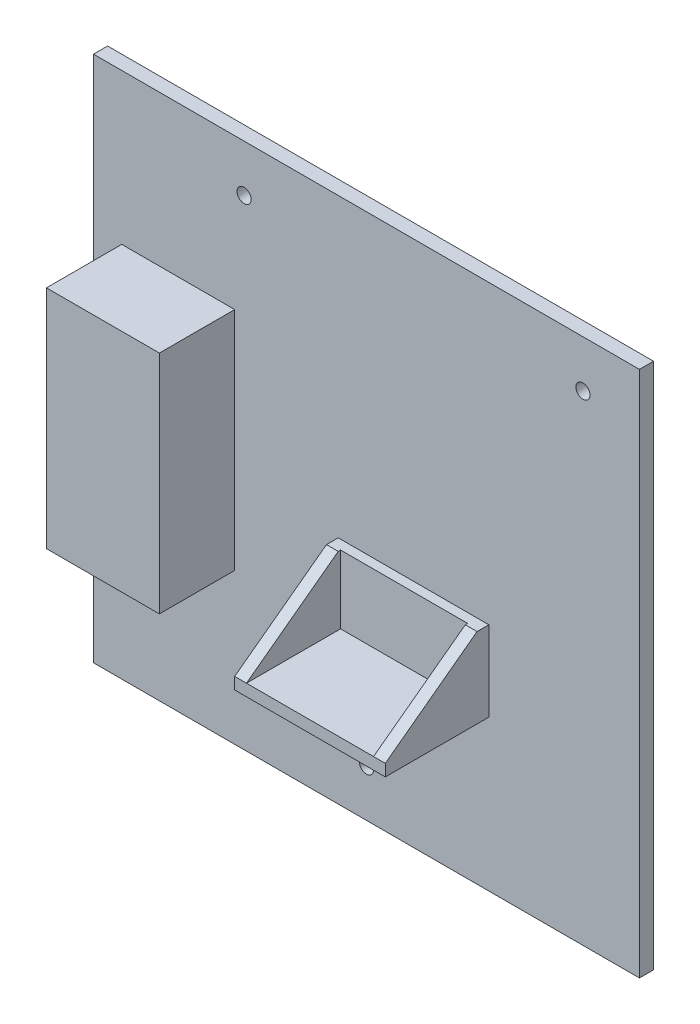
SolidWorks part; units mm, degrees
ref_plane "Alzado" through (0, 0, 0) normal (0, 0, 1) x (1, 0, 0)
ref_plane "Planta" through (0, 0, 0) normal (0, 1, 0) x (1, 0, 0)
ref_plane "Vista lateral" through (0, 0, 0) normal (1, 0, 0) x (0, 0, -1)
sketch "Croquis1" plane through (0, 0, 0) normal (0, 0, 1) x (1, 0, 0)
  line L1 (-58, -56) -> (58, -56)
  line L2 (-58, -56) -> (-58, 56)
  line L3 (-58, 56) -> (58, 56)
  line L4 (58, -56) -> (58, 56)
  line L5 (-58, -56) -> (58, 56) construction
  line L6 (-58, 56) -> (58, -56) construction
  point P0 (0, 0)
  dimension "D1" = 112
  dimension "D2" = 116
extrude "Saliente-Extruir1" add sketch "Croquis1" along normal blind 3
sketch "Croquis2" plane through (0, 0, 3) normal (0, 0, 1) x (1, 0, 0)
  line L0 (-58, 56) -> (-58, -56) construction
  line L1 (-52, -24) -> (-28, -24)
  line L2 (-52, -24) -> (-52, 24)
  line L3 (-52, 24) -> (-28, 24)
  line L4 (-28, -24) -> (-28, 24)
  line L5 (-52, -24) -> (-28, 24) construction
  line L6 (-52, 24) -> (-28, -24) construction
  line L7 (-58, -56) -> (58, -56) construction
  point P0 (-40, 0)
  dimension "D1" = 6
  dimension "D2" = 32
  dimension "D3" = 24
  dimension "D4" = 48
extrude "Saliente-Extruir2" add sketch "Croquis2" along normal blind 16
sketch "Croquis3" plane through (0, 0, 3) normal (0, 0, 1) x (1, 0, 0)
  line L0 (-6, -24) -> (26, -24)
  line L1 (-6, -24) -> (-6, -7)
  line L2 (-6, -7) -> (26, -7)
  line L3 (26, -7) -> (26, -24)
  dimension "D1" = 22
  dimension "D2" = 32
  dimension "D3" = 17
extrude "Saliente-Extruir3" add sketch "Croquis3" along normal blind 22
shell "Vaciado1" thickness 2.5 removed face at (10, -7, 14) removed face at (10, -15.5, 25)
sketch "Croquis5" plane through (0, -21.5, 0) normal (0, 1, 0) x (1, 0, 0)
  line L7 (-3.5, -2.5) -> (23.5, -2.5)
  line L8 (23.5, -2.5) -> (23.5, -5)
  line L9 (23.5, -25) -> (23.5, -2.5) construction
  line L10 (23.5, -5) -> (-3.5, -5)
  line L11 (-3.5, -25) -> (-3.5, -2.5) construction
  line L12 (-3.5, -5) -> (-3.5, -2.5)
  dimension "D1" = 2.5
extrude "Saliente-Extruir7" add sketch "Croquis5" along normal blind 14.5
sketch "Croquis6" plane through (26, 0, 0) normal (1, 0, 0) x (0, 0, -1)
  line L0 (-25, -24) -> (-25, -21.5)
  line L1 (-25, -24) -> (-25, -7) construction
  line L2 (-3, -7) -> (-5.5, -7)
  line L3 (-25, -7) -> (-3, -7) construction
  line L4 (-25, -21.5) -> (-5.5, -7)
  line L5 (-25, -7) -> (-25, -21.5)
  line M4 (-3, -7) -> (-25, -7)
  line M5 (-25, -7) -> (-25, -24)
  dimension "D1" = 2.5
  dimension "D2" = 2.5
extrude "Cortar-Extruir1" cut sketch "Croquis6" against normal blind 34.5 contours L4 M5 M4 region at (26, -11.8333, 18.5)
sketch "Croquis7" plane through (0, 0, 3) normal (0, 0, 1) x (1, 0, 0)
  line L0 (-58, 56) -> (-58, -56) construction
  line L1 (58, 56) -> (-58, 56) construction
  line L2 (-58, -56) -> (58, -56) construction
  circle A0 centre (-26, 46) radius 1.5
  circle A1 centre (46, 46) radius 1.5
  circle A2 centre (0, -46) radius 1.5
  dimension "D2" = 72
  dimension "D3" = 3
  dimension "D4" = 3
  dimension "D5" = 10
  dimension "D6" = 10
  dimension "D7" = 3
  dimension "D8" = 10
  dimension "D9" = 58
  dimension "D1" = 32
extrude "Cortar-Extruir2" cut sketch "Croquis7" against normal blind 34.5
